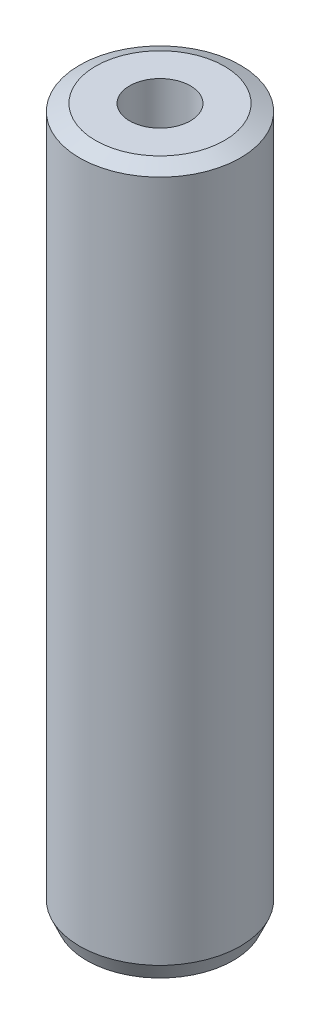
SolidWorks part; units mm, degrees
ref_plane "Front Plane" through (0, 0, 0) normal (0, 0, 1) x (1, 0, 0)
ref_plane "Top Plane" through (0, 0, 0) normal (0, 1, 0) x (1, 0, 0)
ref_plane "Right Plane" through (0, 0, 0) normal (1, 0, 0) x (0, 0, -1)
sketch "Sketch1" plane through (0, 0, 0) normal (0, 1, 0) x (1, 0, 0)
  circle A0 centre (0, 0) radius 55
  dimension "SHAFT_OD" = 110
extrude "Boss-Extrude1" add sketch "Sketch1" along normal blind 482.7211
sketch "Sketch2" plane through (0, 0, 0) normal (0, 1, 0) x (1, 0, 0)
  circle A0 centre (0, 0) radius 20.8015
  dimension "BORE_D" = 41.603
extrude "Cut-Extrude1" cut sketch "Sketch2" along normal through all
chamfer "Chamfer1" distance 4.8464 angle 66.085 2 edges at (0, 482.7211, 55) (0, 0, 55) first distance on face at (0, 482.7211, 55) first distance on face at (0, 0, 20.8015)
